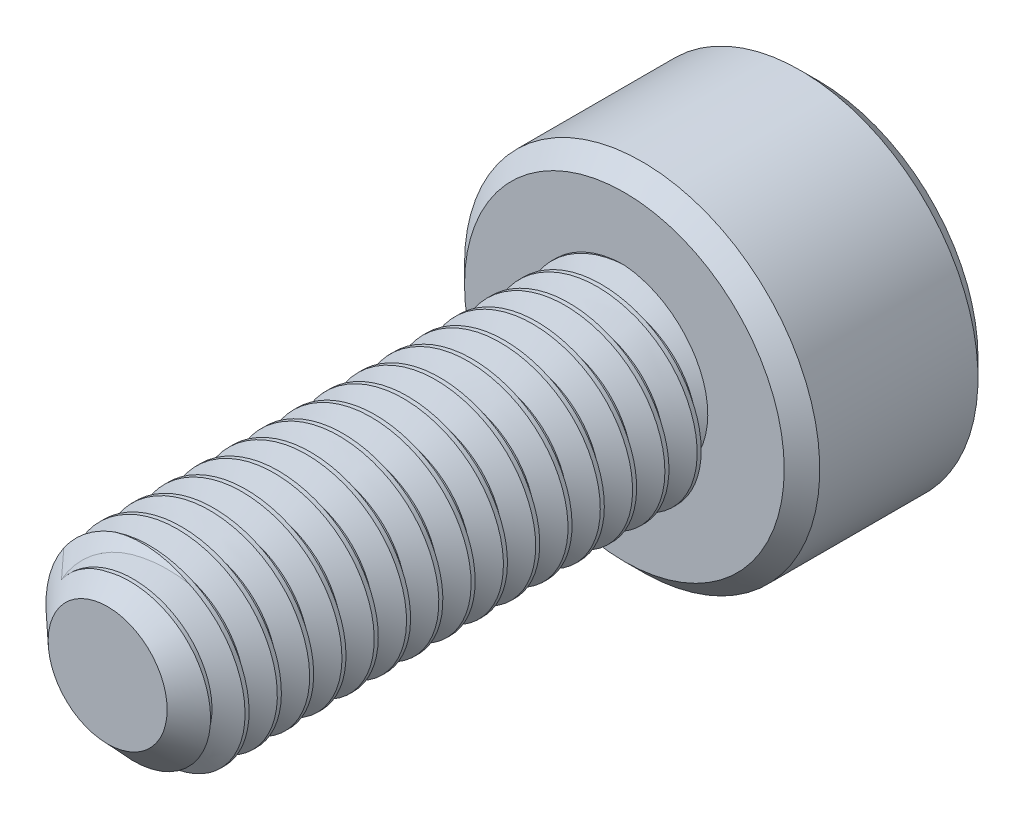
SolidWorks part; units mm, degrees
ref_plane "Front Plane" through (0, 0, 0) normal (0, 0, 1) x (1, 0, 0)
ref_plane "Top Plane" through (0, 0, 0) normal (0, 1, 0) x (1, 0, 0)
ref_plane "Right Plane" through (0, 0, 0) normal (1, 0, 0) x (0, 0, -1)
sketch "Sketch1" plane through (0, 0, 0) normal (0, 0, 1) x (1, 0, 0)
  circle A0 centre (0, 0) radius 1.5
  dimension "OD" = 3
extrude "Extrude1" add sketch "Sketch1" against normal blind 8
sketch "Sketch2" plane through (0, 0, 0) normal (0, 0, 1) x (1, 0, 0)
  circle A0 centre (0, 0) radius 1.5 construction
  circle A1 centre (0, 0) radius 1.5
curve "Helix/Spiral1" pitch 0.5 height 8.5 radius 1.5 centre (0, 0, 0) axis (0, 0, -1) start towards (0, 1, 0) parameters "pitch"=0.5
sketch "Sketch3" plane through (0, 0, 0) normal (1, 0, 0) x (0, 0, -1)
  line L0 (-0.4375, 1.5) -> (-0.25, 1.1752)
  line L1 (-0.25, 1.1752) -> (-0.1875, 1.1752)
  line L2 (-0.1875, 1.1752) -> (0, 1.5)
  line L3 (-0.4375, 1.5) -> (0, 1.5)
  line L4 (-0.2187, 1.5) -> (-0.2187, 1.1752) construction
  line L5 (-0.3438, 1.3376) -> (-0.0937, 1.3376) construction
  line L6 (0, 1.5) -> (0, -1.5) construction
  dimension "D1" = 0.0625
  dimension "D2" = 0.25
  dimension "D3" = 60
sweep "Cut-Sweep1" cut profiles "Sketch3" path "Helix/Spiral1"
sketch "Sketch4" plane through (0, 0, 0) normal (1, 0, 0) x (0, 0, -1)
  line L0 (0.5397, 1.5) -> (0, 0.9212)
  line L1 (0, 0.9212) -> (0, 1.5)
  line L2 (0.5397, 1.5) -> (0, 1.5)
  line L3 (-0.4375, 1.5) -> (0, 1.5) construction
  line L4 (0, 0) -> (7.0209, 0) construction
  dimension "D1" = 47
  dimension "D2" = 0.254
revolve "Cut-Revolve1" cut sketch "Sketch4" angle 360 about L4
sketch "Sketch5" plane through (0, 0, 0) normal (1, 0, 0) x (0, 0, -1)
  line L0 (8, -1.1822) -> (8, 1.0703) construction
  line L1 (8, 1.627) -> (28.1202, 1.627)
  line L2 (8, 1.627) -> (8, 0)
  line L3 (8, 0) -> (28, 0)
  line L4 (28, 1.2968) -> (28, 0)
  line L5 (28.1202, 1.627) -> (28, 1.2968)
  line L6 (0, 0) -> (9.9695, 0) construction
  point P3 (28, 1.627)
  point P10 (28, 1.627)
  dimension "D1" = 0.3302
  dimension "Thread min" = 28
  dimension "D2" = 0.127
  dimension "D3" = 20
revolve "partially thread" [suppressed] add sketch "Sketch5" angle 360 about L6
sketch "Sketch6" plane through (0, 0, -8) normal (0, 0, -1) x (-1, 0, 0)
  circle A0 centre (0, 0) radius 2.75
  dimension "head dia" = 5.5
extrude "Extrude2" add sketch "Sketch6" along normal blind 3
sketch "Sketch7" plane through (0, 0, -11) normal (0, 0, -1) x (-1, 0, 0)
  line L1 (0, 1.4434) -> (-1.25, 0.7217)
  line L2 (-1.25, 0.7217) -> (-1.25, -0.7217)
  line L3 (-1.25, -0.7217) -> (0, -1.4434)
  line L4 (0, -1.4434) -> (1.25, -0.7217)
  line L5 (1.25, -0.7217) -> (1.25, 0.7217)
  line L6 (1.25, 0.7217) -> (0, 1.4434)
  circle A0 centre (0, 0) radius 1.25 construction
  dimension "hex dia" = 2.5
extrude "Cut-Extrude1" cut sketch "Sketch7" against normal blind 1.875
sketch "Sketch8" plane through (0, 0, -11) normal (0, 0, -1) x (-1, 0, 0)
  circle A0 centre (0, 0) radius 1.4434
extrude "Cut-Extrude2" cut sketch "Sketch8" against normal through all draft 45
chamfer "Chamfer1" distance 0.275 angle 45 2 edges at (-2.75, 0, -11) (-2.75, 0, -8)
sketch "Sketch9" plane through (0, 0, 0) normal (1, 0, 0) x (0, 0, -1)
  line L0 (0, 1.5) -> (0, -1.5) construction
  line L1 (2.75, 1.5) -> (2.75, -1.5) construction
  dimension "D1" = 2.75
equation "\"D3@Helix/Spiral1\" = \"screw length@Extrude1\"+\"pitch@Helix/Spiral1\""
equation "\"D1@Sketch3\" = \"pitch@Helix/Spiral1\"*.125"
equation "\"D2@Sketch3\" = \"pitch@Helix/Spiral1\"*.5"
equation "\"D1@Cut-Extrude1\" = \"hex dia@Sketch7\"*.75"
equation "\"D1@Chamfer1\" = \"head dia@Sketch6\"*.05"
equation "\"D1@Sketch9\" = \"pitch@Helix/Spiral1\"*5.5"
